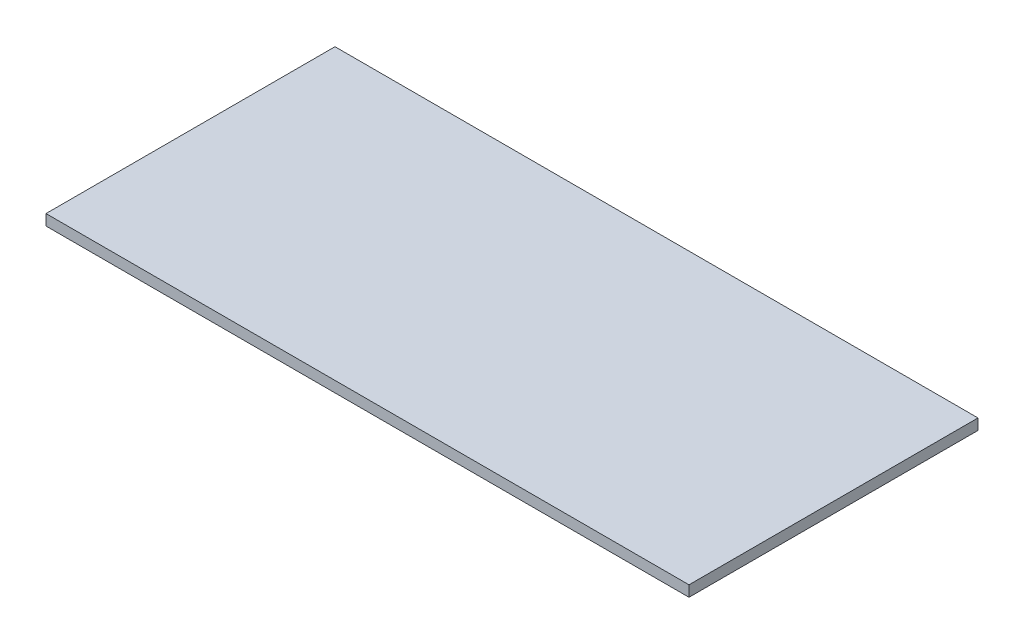
SolidWorks part; units mm, degrees
ref_plane "Front Plane" through (0, 0, 0) normal (0, 0, 1) x (1, 0, 0)
ref_plane "Top Plane" through (0, 0, 0) normal (0, 1, 0) x (1, 0, 0)
ref_plane "Right Plane" through (0, 0, 0) normal (1, 0, 0) x (0, 0, -1)
sketch "Sketch1" plane through (0, 0, 0) normal (0, 1, 0) x (1, 0, 0)
  line L1 (0, 0) -> (89, 0)
  line L2 (0, 0) -> (0, 40)
  line L3 (0, 40) -> (89, 40)
  line L4 (89, 0) -> (89, 40)
  dimension "D1" = 40
  dimension "D2" = 89
extrude "Boss-Extrude1" add sketch "Sketch1" along normal blind 1.5
